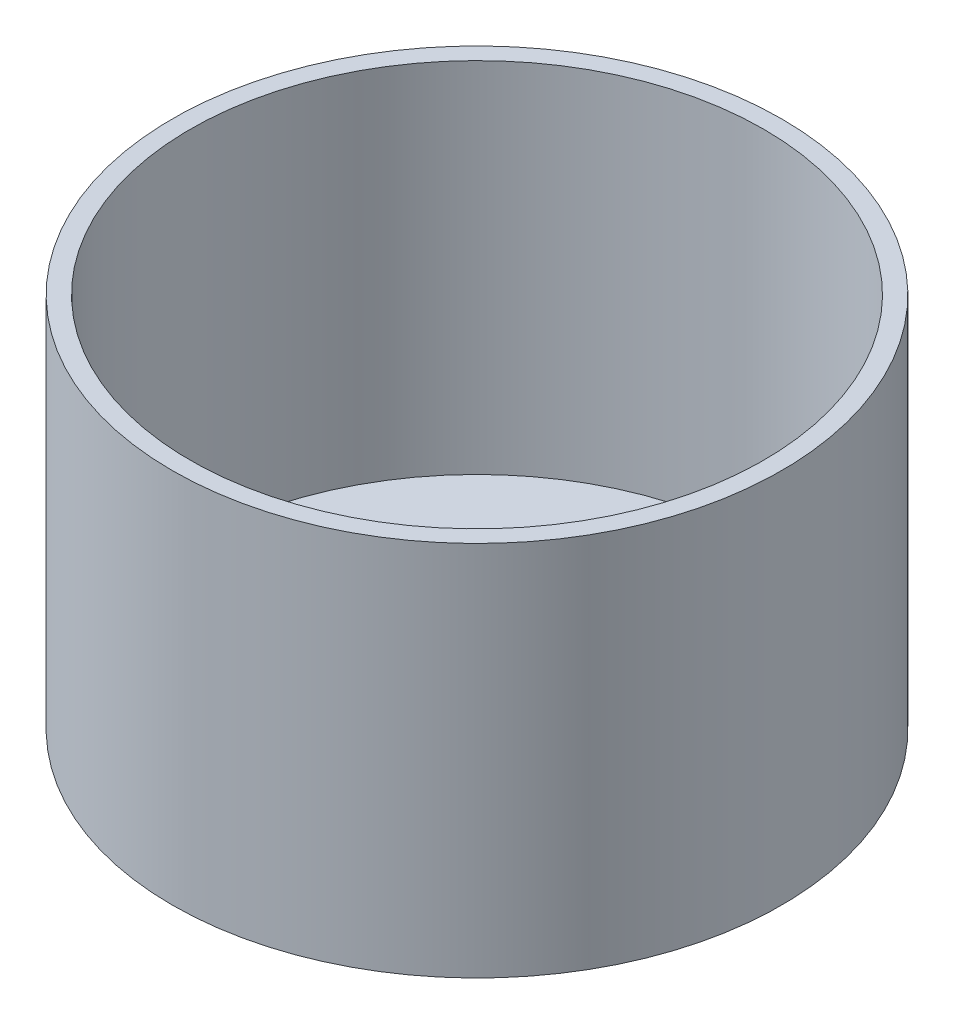
SolidWorks part; units mm, degrees
ref_plane "Front Plane" through (0, 0, 0) normal (0, 0, 1) x (1, 0, 0)
ref_plane "Top Plane" through (0, 0, 0) normal (0, 1, 0) x (1, 0, 0)
ref_plane "Right Plane" through (0, 0, 0) normal (1, 0, 0) x (0, 0, -1)
sketch "Compartment" plane through (0, 0, 0) normal (0, 0, 1) x (1, 0, 0)
  line L3 (85, -80) -> (0, -80)
  line L6 (80, 25) -> (85, 25)
  line L9 (80, 25) -> (80, -75)
  line L10 (80, -75) -> (0, -75)
  line L11 (0, -75) -> (0, -80)
  line L14 (85, 25) -> (85, -80)
  dimension "D1" = 100
  dimension "D2" = 5
  dimension "D5" = 80
  dimension "D6" = 5
  dimension "D9" = 80
ref_axis "Axis1" through (0, 0, 0) along (0, 1, 0)
revolve "Revolve1" add sketch "Compartment" angle 360 about axis through (0, 0, 0) along (0, 1, 0)
sketch "Motor Hole" plane through (0, -80, 0) normal (0, -1, 0) x (1, 0, 0)
  circle A0 centre (0, 0) radius 4.5
  dimension "D1" = 9
extrude "Cut-Extrude2" cut sketch "Motor Hole" against normal up to next
